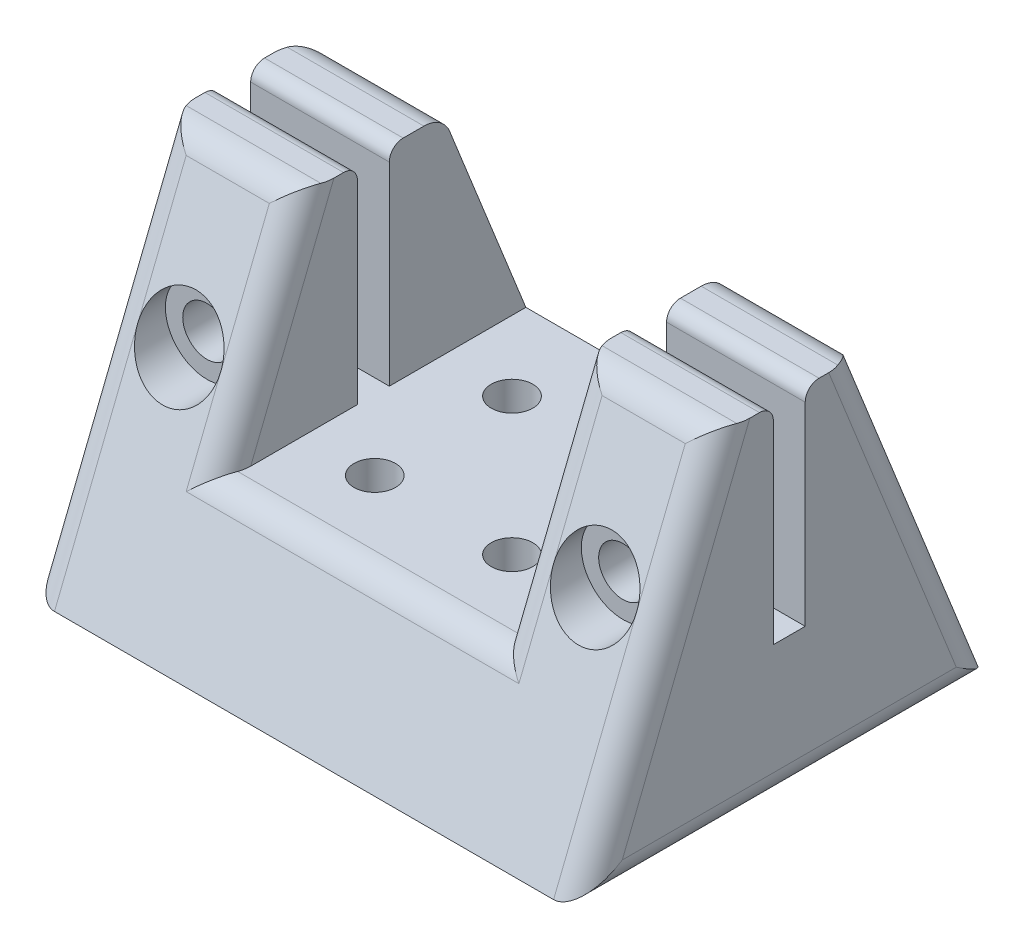
SolidWorks part; units mm, degrees
ref_plane "Спереди" through (0, 0, 0) normal (0, 0, 1) x (1, 0, 0)
ref_plane "Сверху" through (0, 0, 0) normal (0, 1, 0) x (1, 0, 0)
ref_plane "Справа" through (0, 0, 0) normal (1, 0, 0) x (0, 0, -1)
sketch "Эскиз1" plane through (0, 0, 0) normal (0, 1, 0) x (1, 0, 0)
  line L0 (13, 15) -> (20, 22) construction
  line L1 (0, 0) -> (40, 0)
  line L2 (0, 0) -> (0, 30)
  line L3 (0, 30) -> (40, 30)
  line L4 (40, 0) -> (40, 30)
  line L5 (24.9497, 10.0503) -> (15.0503, 19.9497) construction
  line L6 (15.0503, 10.0503) -> (24.9497, 19.9497) construction
  circle A0 centre (20, 15) radius 7 construction
  circle A1 centre (15.0503, 19.9497) radius 1.5
  circle A2 centre (24.9497, 19.9497) radius 1.5
  circle A3 centre (24.9497, 10.0503) radius 1.5
  circle A4 centre (15.0503, 10.0503) radius 1.5
  circle A5 centre (20, 15) radius 8.5 construction
  point P7 (40, 15)
  dimension "D1" = 40
  dimension "D3" = 14
  dimension "D6" = 17
  dimension "D2" = 30
  dimension "D4" = 20
  dimension "D5" = 15
extrude "Бобышка-Вытянуть1" add sketch "Эскиз1" along normal blind 25
sketch "Эскиз3" plane through (0, 25, 0) normal (0, 1, 0) x (1, 0, 0)
  line L0 (40, 30) -> (0, 30) construction
  line L1 (10, 30) -> (30, 30)
  line L2 (10, 30) -> (10, 0)
  line L3 (10, 0) -> (30, 0)
  line L4 (30, 30) -> (30, 0)
  line L5 (0, 0) -> (40, 0) construction
  line L6 (0, 30) -> (0, 0) construction
  dimension "D1" = 20
  dimension "D2" = 10
extrude "Вырез-Вытянуть2" cut sketch "Эскиз3" against normal blind 15
sketch "Эскиз4" plane through (0, 0, 0) normal (-1, 0, 0) x (0, 0, 1)
  line L0 (-30, 0) -> (-20, 25)
  line L1 (-30, 25) -> (0, 25) construction
  line L2 (-30, 25) -> (-30, 0) construction
  line L3 (-20, 25) -> (-30, 25)
  line L4 (-10, 25) -> (0, 0)
  line L5 (0, 25) -> (0, 0) construction
  line L6 (-30, 25) -> (-30, 0)
  line L7 (-10, 25) -> (0, 25)
  line L8 (0, 25) -> (0, 0)
  line L9 (-16.15, 25) -> (-16.15, 10)
  line L10 (-16.15, 10) -> (-13.85, 10)
  line L11 (-13.85, 10) -> (-13.85, 25)
  line L12 (-13.85, 25) -> (-16.15, 25)
  point P21 (-15, 25)
  point P22 (-15, 25)
  dimension "D1" = 10
  dimension "D2" = 10
  dimension "D3" = 2.3
  dimension "D5" = 15
extrude "Вырез-Вытянуть3" cut sketch "Эскиз4" against normal through all
ref_plane "Плоскость1" through (0, 0, -30) normal (0, 0, 1) x (-1, 0, 0)
sketch "Эскиз6" plane through (0, 0, -30) normal (0, 0, 1) x (-1, 0, 0)
  line L0 (-5, -15) -> (-35, -15) construction
  line L1 (-5, -16.75) -> (-35, -16.75) construction
  line L3 (0, 0) -> (-40, 0) construction
  circle A0 centre (-5, -15) radius 1.75
  circle A1 centre (-35, -15) radius 1.75
  point P9 (-20, 0)
  point P10 (-20, -15)
  dimension "D1" = 3.5
  dimension "D2" = 30
  dimension "D3" = 15
extrude "Вырез-Вытянуть7" cut sketch "Эскиз6" against normal blind 20 and the other way through all
sketch "Эскиз7" plane through (0, 0, -30) normal (0, 0, 1) x (-1, 0, 0)
  line L0 (-35, -15) -> (-5, -15) construction
  line L1 (-35, -12) -> (-5, -12) construction
  circle A0 centre (-5, -15) radius 3
  circle A1 centre (-35, -15) radius 3
  point P0 (-5, -15)
  point P1 (-35, -15)
  dimension "D1" = 6
extrude "Вырез-Вытянуть8" cut sketch "Эскиз7" against normal blind 20 and the other way blind 8
ref_plane "Плоскость2" through (0, 0, 0) normal (0, 0, -1) x (1, 0, 0)
sketch "Эскиз8" plane through (0, 0, 0) normal (0, 0, -1) x (1, 0, 0)
  line L0 (35, -15) -> (5, -15) construction
  line L1 (35, -18) -> (5, -18) construction
  circle A0 centre (5, -15) radius 3
  circle A1 centre (35, -15) radius 3
  point P0 (5, -15)
  point P1 (35, -15)
  dimension "D1" = 6
extrude "Вырез-Вытянуть9" cut sketch "Эскиз8" against normal blind 20 and the other way blind 8
fillet "Скругление3" radius 1 4 edges at (5, 25, -13.85) (35, 25, -13.85) (35, 25, -16.15) (5, 25, -16.15)
fillet "Скругление4" radius 2 13 edges at (5, 25, -20) (35, 25, -20) (5, 25, -10) (35, 25, -10) (0, 0, -15) (40, 0, -15) (0, 12.5, -25) (40, 12.5, -25) (0, 12.5, -5) (40, 12.5, -5) (10, 17.5, -7) (30, 17.5, -7) (20, 10, -4)
